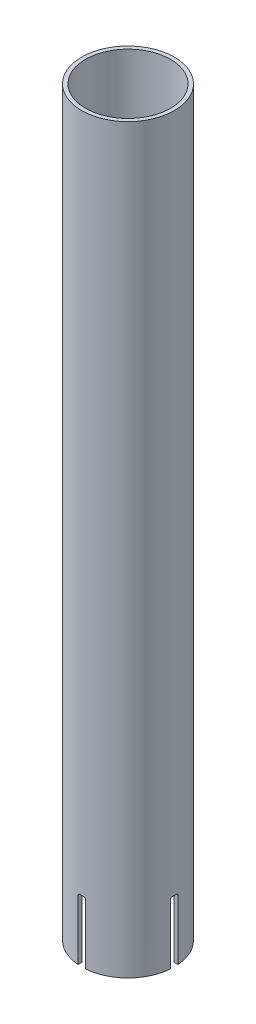
SolidWorks part; units mm, degrees
ref_plane "Front Plane" through (0, 0, 0) normal (0, 0, 1) x (1, 0, 0)
ref_plane "Top Plane" through (0, 0, 0) normal (0, 1, 0) x (1, 0, 0)
ref_plane "Right Plane" through (0, 0, 0) normal (1, 0, 0) x (0, 0, -1)
sketch "Sketch1" plane through (0, 0, 0) normal (0, 0, 1) x (1, 0, 0)
  line L0 (0, 0) -> (0, 304.8) construction
  line L1 (-19.05, 0) -> (-17.4625, 0)
  line L2 (-19.05, 0) -> (-19.05, 304.8)
  line L3 (-19.05, 304.8) -> (-17.4625, 304.8)
  line L4 (19.05, 0) -> (19.05, 304.8)
  line L5 (-17.4625, 0) -> (-17.4625, 304.8)
  line L6 (17.4625, 304.8) -> (17.4625, 0)
  line L7 (17.4625, 0) -> (19.05, 0)
  line L8 (17.4625, 304.8) -> (19.05, 304.8)
  dimension "D1" = 38.1
  dimension "12" = 304.8
  dimension "D2" = 1.5875
revolve "Revolve2" add sketch "Sketch1" angle 360 about L0 region at (-18.2563, 152.4, 0)
sketch "Sketch2" plane through (0, 0, 0) normal (0, 0, 1) x (1, 0, 0)
  line L0 (-17.4625, 0) -> (-17.4625, 304.8) construction
  line L1 (-17.4625, 247.65) -> (17.4625, 247.65)
  line L2 (-17.4625, 247.65) -> (-17.4625, 254)
  line L3 (-17.4625, 254) -> (17.4625, 254)
  line L4 (17.4625, 247.65) -> (17.4625, 254)
  line L5 (17.4625, 304.8) -> (17.4625, 0) construction
  line L6 (17.4625, 304.8) -> (-17.4625, 304.8) construction
  line L7 (0, 247.65) -> (0, 254)
  dimension "D1" = 50.8
  dimension "D2" = 6.35
revolve "Revolve4" add sketch "Sketch2" angle 360 about L0 reverse direction yes
sketch "Sketch3" plane through (0, 0, 0) normal (0, 0, 1) x (1, 0, 0)
  line L0 (-1.5875, 0) -> (-1.5875, 25.4)
  line L1 (-19.05, 0) -> (19.05, 0) construction
  line L2 (-1.5875, 25.4) -> (1.5875, 25.4)
  line L3 (1.5875, 25.4) -> (1.5875, 0)
  line L4 (17.4625, 0) -> (19.05, 0) construction
  line L5 (0, 0) -> (0, 304.8) construction
  line L6 (1.5875, 0) -> (-1.5875, 0)
  dimension "D1" = 3.175
  dimension "D2" = 25.4
extrude "Cut-Extrude2" cut sketch "Sketch3" against normal blind 50.8 contours L6 L0 L2 L3
fillet "Fillet1" radius 0.7937 2 edges at (-1.5875, 25.4, -18.187) (1.5875, 25.4, -18.187)
pattern_circular "CirPattern1" count 4 over 360 about axis through (0, 0, 0) along (0, -1, 0) of "Cut-Extrude2", "Fillet1"
